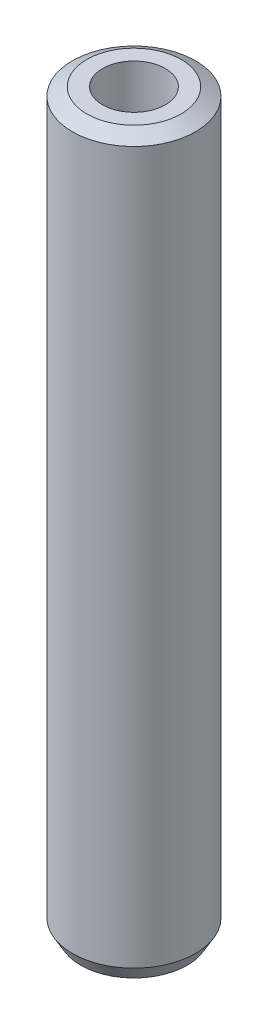
SolidWorks part; units mm, degrees
ref_plane "Front Plane" through (0, 0, 0) normal (0, 0, 1) x (1, 0, 0)
ref_plane "Top Plane" through (0, 0, 0) normal (0, 1, 0) x (1, 0, 0)
ref_plane "Right Plane" through (0, 0, 0) normal (1, 0, 0) x (0, 0, -1)
sketch "Sketch1" plane through (0, 0, 0) normal (0, 1, 0) x (1, 0, 0)
  circle A0 centre (0, 0) radius 30
  dimension "SHAFT_OD" = 60
extrude "Boss-Extrude1" add sketch "Sketch1" along normal blind 357.8251
sketch "Sketch2" plane through (0, 0, 0) normal (0, 1, 0) x (1, 0, 0)
  circle A0 centre (0, 0) radius 15.3156
  dimension "BORE_D" = 30.6313
extrude "Cut-Extrude1" cut sketch "Sketch2" along normal through all
chamfer "Chamfer1" distance 4.043 angle 60 2 edges at (0, 357.8251, 30) (0, 0, 30) first distance on face at (0, 357.8251, 30) first distance on face at (0, 0, 15.3156)
